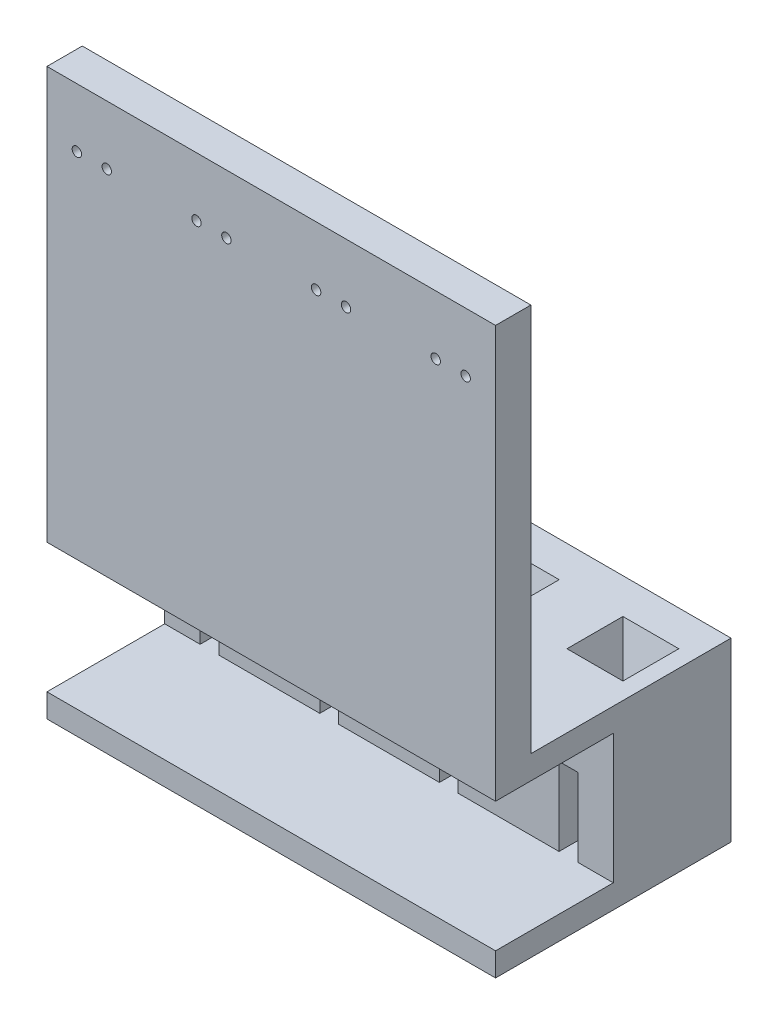
SolidWorks part; units mm, degrees
ref_plane "前基準面" through (0, 0, 0) normal (0, 0, 1) x (1, 0, 0)
ref_plane "上基準面" through (0, 0, 0) normal (0, 1, 0) x (1, 0, 0)
ref_plane "右基準面" through (0, 0, 0) normal (1, 0, 0) x (0, 0, -1)
sketch "草圖1" plane through (0, 0, 0) normal (0, 0, 1) x (1, 0, 0)
  line L1 (-19.05, -24) -> (19.05, -24)
  line L2 (-19.05, -24) -> (-19.05, 24)
  line L3 (-19.05, 24) -> (19.05, 24)
  line L4 (19.05, -24) -> (19.05, 24)
  line L5 (-19.05, -24) -> (19.05, 24) construction
  line L6 (-19.05, 24) -> (19.05, -24) construction
  point P0 (0, 0)
  dimension "D1" = 48
  dimension "D2" = 38.1
extrude "填料-伸長1" add sketch "草圖1" along normal blind 3
sketch "草圖2" plane through (0, 0, 3) normal (0, 0, 1) x (1, 0, 0)
  line L0 (-19.05, 24) -> (-19.05, -24) construction
  line L1 (19.05, 24) -> (-19.05, 24) construction
  circle A0 centre (-16.51, 19) radius 0.4
  circle A1 centre (-13.97, 19) radius 0.4
  circle A2 centre (-6.35, 19) radius 0.4
  circle A3 centre (-3.81, 19) radius 0.4
  circle A4 centre (3.81, 19) radius 0.4
  circle A5 centre (6.35, 19) radius 0.4
  circle A6 centre (13.97, 19) radius 0.4
  circle A7 centre (16.51, 19) radius 0.4
  dimension "D3" = 0.8
  dimension "D1" = 2.54
  dimension "D2" = 5
  dimension "D4" = 2.54
  dimension "D5" = 4
extrude "除料-伸長1" cut sketch "草圖2" against normal through all
sketch "草圖3" plane through (0, 0, 0) normal (0, 0, -1) x (-1, 0, 0)
  line L0 (19.05, 24) -> (19.05, -24) construction
  line L1 (-19.05, -24) -> (19.05, -24)
  line L2 (-19.05, -24) -> (-19.05, -9)
  line L3 (-19.05, -9) -> (19.05, -9)
  line L4 (19.05, -24) -> (19.05, -9)
  dimension "D1" = 15
extrude "填料-伸長2" add sketch "草圖3" along normal blind 17
sketch "草圖4" plane through (0, -9, 0) normal (0, 1, 0) x (1, 0, 0)
  line L0 (-19.05, 17) -> (-19.05, 0) construction
  line L1 (-16.615, 13) -> (-13.865, 13)
  line L2 (-16.615, 13) -> (-16.615, 10.25)
  line L3 (-16.615, 10.25) -> (-13.865, 10.25)
  line L4 (-13.865, 13) -> (-13.865, 10.25)
  line L7 (19.05, -3) -> (-19.05, -3) construction
  line L8 (-6.455, 13) -> (-3.705, 13)
  line L9 (-6.455, 13) -> (-6.455, 10.25)
  line L10 (-6.455, 10.25) -> (-3.705, 10.25)
  line L11 (-3.705, 13) -> (-3.705, 10.25)
  line L12 (3.705, 13) -> (6.455, 13)
  line L13 (3.705, 13) -> (3.705, 10.25)
  line L14 (3.705, 10.25) -> (6.455, 10.25)
  line L15 (6.455, 13) -> (6.455, 10.25)
  line L16 (13.865, 13) -> (16.615, 13)
  line L17 (13.865, 13) -> (13.865, 10.25)
  line L18 (13.865, 10.25) -> (16.615, 10.25)
  line L19 (16.615, 13) -> (16.615, 10.25)
  point P4 (-15.24, 10.25)
  dimension "D1" = 3.81
  dimension "D2" = 2.75
  dimension "D3" = 16
  dimension "D4" = 4
extrude "除料-伸長2" cut sketch "草圖4" against normal blind 4
chamfer "導角1" distance 1 distance2 4 16 edges at (-15.24, -9, -13) (-13.865, -9, -11.625) (-16.615, -9, -11.625) (-15.24, -9, -10.25) (15.24, -9, -10.25) (13.865, -9, -11.625) (16.615, -9, -11.625) (15.24, -9, -13) (5.08, -9, -10.25) (6.455, -9, -11.625) (5.08, -9, -13) (3.705, -9, -11.625) (-5.08, -9, -10.25) (-6.455, -9, -11.625) (-5.08, -9, -13) (-3.705, -9, -11.625) first distance on face at (-5.08, -9, -11.625)
sketch "草圖5" plane through (0, -24, 0) normal (0, -1, 0) x (1, 0, 0)
  line L0 (-16.615, -13) -> (-16.615, -10.25) construction
  line L1 (-16.615, -13) -> (-16.615, -10.25) construction
  line L4 (-19.05, 3) -> (-19.05, -17)
  line L5 (-19.05, -17) -> (19.05, -17)
  line L6 (19.05, -17) -> (19.05, 3)
  line L7 (19.05, 3) -> (-19.05, 3)
  line L8 (-19.05, 3) -> (-19.05, -17)
  line L9 (-19.05, -17) -> (19.05, -17)
  line L10 (19.05, -17) -> (19.05, 3)
  line L11 (19.05, 3) -> (-19.05, 3)
  circle A0 centre (-15.24, -11.625) radius 0.8
  circle A1 centre (-5.08, -11.625) radius 0.8
  circle A2 centre (5.08, -11.625) radius 0.8
  circle A3 centre (15.24, -11.625) radius 0.8
  point P14 (0, 0)
  point P15 (-16.615, -11.625)
  dimension "D3" = 1.6
  dimension "D5" = 3.81
  dimension "D1" = 0
  dimension "D2" = 4
extrude "除料-伸長5" cut sketch "草圖5" against normal through all contours A0 | A1 | A2 | A3
sketch "草圖6" plane through (0, 0, 3) normal (0, 0, 1) x (1, 0, 0)
  line L0 (-19.05, 24) -> (-19.05, -24) construction
  line L1 (19.05, -24) -> (19.05, 24) construction
  line L3 (-19.05, -11) -> (19.05, -11)
  line L4 (-19.05, -11) -> (19.05, -11)
  line L5 (-19.05, -11) -> (-19.05, -22)
  line L6 (-19.05, -22) -> (19.05, -22)
  line L7 (-19.05, -22) -> (19.05, -22)
  line L8 (19.05, -11) -> (19.05, -22)
  dimension "D2" = 2
  dimension "D1" = 2
extrude "除料-伸長6" cut sketch "草圖6" against normal blind 10
sketch "草圖8" plane through (0, 0, -7) normal (0, 0, 1) x (1, 0, 0)
  line L0 (-16.04, -15.3774) -> (-16.04, -22)
  line L1 (-16.04, -13) -> (-16.04, -24) construction
  line L2 (-19.05, -22) -> (19.05, -22) construction
  line L3 (-16.04, -22) -> (-14.44, -22)
  line L4 (-14.44, -24) -> (-14.44, -13) construction
  line L5 (-14.44, -22) -> (-14.44, -15.3774)
  line L6 (-14.44, -15.3774) -> (-16.04, -15.3774)
  line L7 (-16.615, -13) -> (-13.865, -13) construction
  line L8 (-5.88, -15.3774) -> (-5.88, -22)
  line L9 (-5.88, -22) -> (-4.28, -22)
  line L10 (-4.28, -22) -> (-4.28, -15.3774)
  line L11 (-4.28, -15.3774) -> (-5.88, -15.3774)
  line L12 (4.28, -15.3774) -> (4.28, -22)
  line L13 (4.28, -22) -> (5.88, -22)
  line L14 (5.88, -22) -> (5.88, -15.3774)
  line L15 (5.88, -15.3774) -> (4.28, -15.3774)
  line L16 (14.44, -15.3774) -> (14.44, -22)
  line L17 (14.44, -22) -> (16.04, -22)
  line L18 (16.04, -22) -> (16.04, -15.3774)
  line L19 (16.04, -15.3774) -> (14.44, -15.3774)
  point P12 (-15.24, -13)
  dimension "D1" = 2.3774
  dimension "D2" = 4
extrude "除料-伸長7" cut sketch "草圖8" against normal up to next
